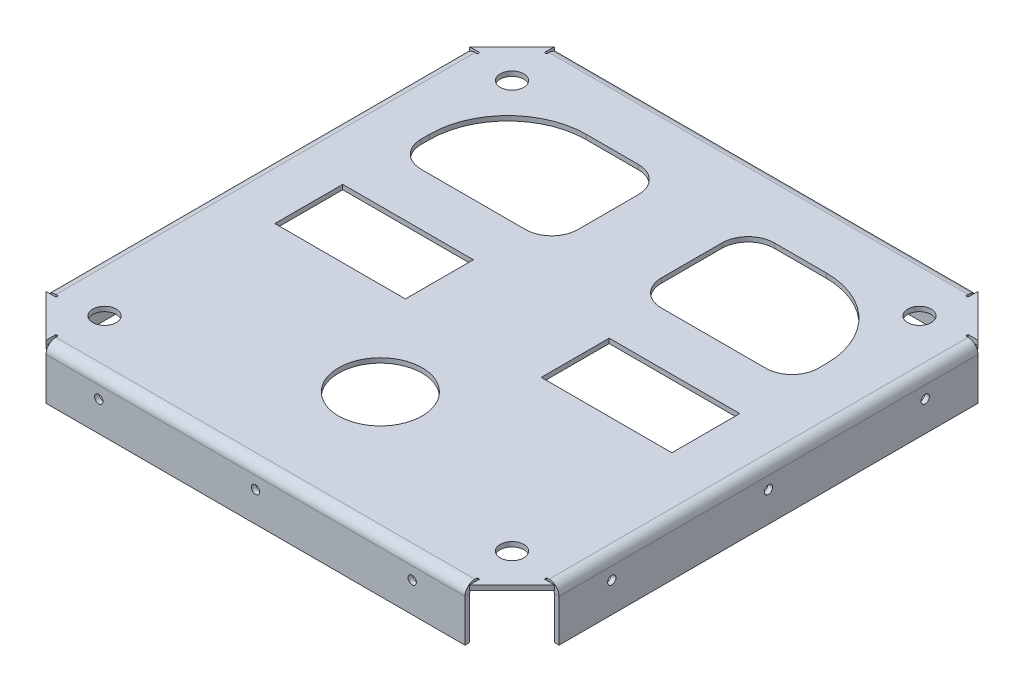
SolidWorks part; units mm, degrees
note: The reader was unsure of these and kept them because the rebuilt part matched: flange length of "Edge-Flange1".
material "6061 Alloy"
ref_plane "Front Plane" through (0, 0, 0) normal (0, 0, 1) x (1, 0, 0)
ref_plane "Top Plane" through (0, 0, 0) normal (0, 1, 0) x (1, 0, 0)
ref_plane "Right Plane" through (0, 0, 0) normal (1, 0, 0) x (0, 0, -1)
sketch "Sketch1" plane through (0, 0, 0) normal (0, 1, 0) x (1, 0, 0)
  line L0 (9, 98.2) -> (0, 89.2)
  line L1 (9, 98.2) -> (89.2, 98.2)
  line L2 (0, 89.2) -> (0, 9)
  line L3 (9, 0) -> (89.2, 0)
  line L4 (98.2, 89.2) -> (98.2, 9)
  line L5 (89.2, 98.2) -> (98.2, 89.2)
  line L6 (98.2, 9) -> (89.2, 0)
  line L7 (9, 0) -> (0, 9)
  line L8 (49.1, 98.2) -> (49.1, 0) construction
  line L9 (87.1, 54.7) -> (87.1, 41.7)
  line L10 (36.1, 54.7) -> (11.1, 54.7)
  line L11 (36.1, 54.7) -> (36.1, 41.7)
  line L12 (36.1, 41.7) -> (11.1, 41.7)
  line L13 (11.1, 54.7) -> (11.1, 41.7)
  line L14 (62.1, 41.7) -> (87.1, 41.7)
  line L15 (62.1, 54.7) -> (62.1, 41.7)
  line L16 (62.1, 54.7) -> (87.1, 54.7)
  dimension "D1" = 98.2
  dimension "D2" = 98.2
  dimension "D3" = 9
  dimension "D4" = 9
  dimension "D5" = 9
  dimension "D6" = 9
  dimension "D7" = 43.5
  dimension "D8" = 56.5
  dimension "D9" = 13
  dimension "D10" = 38
base flange "Base-Flange1" sketch "Sketch1" thickness 0.9 reverse thickness direction no parameters "D1"=1
edge flange "Edge-Flange1" sketch "Sketch14" flange profiles "Sketch14", "Sketch15", "Sketch16", "Sketch17" flange angle 90 flange length 10 flange position material inside bend radius 1 thickness 0.9 relief rectangular parameters "D6"=10, "D8"=1
sketch "Sketch14" plane through (98.2, -0.9, 0) normal (-1, 0, 0) x (0, 0, -1)
  line L1 (89.2, 0) -> (9, 0) construction
  line L2 (9, 0) -> (9, 9.1)
  line L3 (9, 9.1) -> (89.2, 9.1)
  line L4 (89.2, 9.1) -> (89.2, 0)
  line L5 (89.2, 0) -> (9, 0)
sketch "Sketch15" plane through (0, -0.9, 0) normal (0, 0, -1) x (1, 0, 0)
  line L0 (89.2, 0) -> (9, 0) construction
  line L1 (89.2, 0) -> (9, 0)
  line L2 (89.2, 0) -> (89.2, 9.1)
  line L3 (89.2, 9.1) -> (9, 9.1)
  line L4 (9, 9.1) -> (9, 0)
sketch "Sketch16" plane through (0, -0.9, 0) normal (1, 0, 0) x (0, 0, 1)
  line L0 (-9, 0) -> (-89.2, 0) construction
  line L1 (-9, 0) -> (-89.2, 0)
  line L2 (-9, 0) -> (-9, 9.1)
  line L3 (-9, 9.1) -> (-89.2, 9.1)
  line L4 (-89.2, 9.1) -> (-89.2, 0)
sketch "Sketch17" plane through (0, -0.9, -98.2) normal (0, 0, 1) x (-1, 0, 0)
  line L0 (-9, 0) -> (-89.2, 0) construction
  line L1 (-9, 0) -> (-89.2, 0)
  line L2 (-9, 0) -> (-9, 9.1)
  line L3 (-9, 9.1) -> (-89.2, 9.1)
  line L4 (-89.2, 9.1) -> (-89.2, 0)
bend "EdgeBend1" bend radius 1 bend angle 90 parameters "D5"=1
bend "EdgeBend2" bend radius 1 bend angle 90 parameters "D5"=2
bend "EdgeBend3" bend radius 1 bend angle 90 parameters "D5"=3
bend "EdgeBend4" bend radius 1 bend angle 90 parameters "D5"=4
sketch "Sketch18" plane through (0, 0, 0) normal (0, 1, 0) x (1, 0, 0)
  line L1 (9, 1.9) -> (89.2, 1.9) construction
  line L5 (11.1, 69.7) -> (11.1, 71.3)
  line L6 (89.2, 96.3) -> (9, 96.3) construction
  line L7 (26.1, 86.3) -> (36.1, 86.3)
  line L8 (41.1, 81.3) -> (41.1, 69.7)
  line L9 (36.1, 64.7) -> (16.1, 64.7)
  line L10 (49.1, 96.3) -> (49.1, 1.9) construction
  line L12 (62.1, 64.7) -> (82.1, 64.7)
  line L13 (57.1, 81.3) -> (57.1, 69.7)
  line L14 (72.1, 86.3) -> (62.1, 86.3)
  line L15 (87.1, 69.7) -> (87.1, 71.3)
  line L18 (36.1, 54.7) -> (11.1, 54.7) construction
  circle A0 centre (49.1, 23.9) radius 8
  arc A4 (36.1, 64.7) -> (41.1, 69.7) centre (36.1, 69.7) ccw
  arc A5 (16.1, 64.7) -> (11.1, 69.7) centre (16.1, 69.7) cw
  arc A7 (36.1, 86.3) -> (41.1, 81.3) centre (36.1, 81.3) cw
  arc A8 (62.1, 86.3) -> (57.1, 81.3) centre (62.1, 81.3) ccw
  arc A10 (82.1, 64.7) -> (87.1, 69.7) centre (82.1, 69.7) ccw
  arc A11 (62.1, 64.7) -> (57.1, 69.7) centre (62.1, 69.7) cw
  arc A16 (11.1, 71.3) -> (26.1, 86.3) centre (26.1, 71.3) cw
  arc A17 (87.1, 71.3) -> (72.1, 86.3) centre (72.1, 71.3) ccw
  dimension "D8" = 15
  dimension "D9" = 15
  dimension "D4" = 16
  dimension "D1" = 10
  dimension "D2" = 10
  dimension "D3" = 8
  dimension "D5" = 22
extrude "Cut-Extrude1" cut sketch "Sketch18" against normal blind 10 normal cut yes
hole_wizard "M2x0.4 Tapped Hole1" positions "Sketch21" profile "Sketch22" tap size "M2x0.4" standard "ANSI Metric"
sketch "Sketch21" plane through (102.3843, -9.7238, 0) normal (0, 0, 1) x (1, 0, 0)
  point P0 (-83.2843, 5.4738)
  point P1 (-53.2843, 5.4738)
  point P2 (-23.2843, 5.4738)
cosmetic thread "Hole Thread1"
cosmetic thread "Hole Thread2"
cosmetic thread "Hole Thread3"
sketch "Sketch22" plane through (19.1, -4.25, 0) normal (1, 0, 0) x (0, -1, 0)
  line L0 (0, 0) -> (0, 5.6807)
  line L1 (0, 5.6807) -> (0.8, 5.2)
  line L2 (0.8, 5.2) -> (0.8, 0)
  line L5 (0.8, 0) -> (0, 0)
  line L10 (0, 5.6807) -> (-0.8, 5.2) construction
  line L11 (0, -6.35) -> (0, 107.95) construction
  dimension "Tap Drill Dia." = 1.6
  dimension "Tap Drill Depth" = 5.2
  dimension "Drill Angle" = 118
hole_wizard "M2x0.4 Tapped Hole2" positions "Sketch23" profile "Sketch24" tap size "M2x0.4" standard "ANSI Metric"
sketch "Sketch23" plane through (0, -9.7238, -74.0081) normal (-1, 0, 0) x (0, 0, 1)
  point P0 (54.9081, 5.4738)
  point P1 (24.9081, 5.4738)
  point P2 (-5.0919, 5.4738)
sketch "Sketch24" plane through (0, -4.25, -19.1) normal (0, 1, 0) x (0, 0, 1)
  line L0 (0, 0) -> (0, 5.6807)
  line L1 (0, 5.6807) -> (0.8, 5.2)
  line L2 (0.8, 5.2) -> (0.8, 0)
  line L5 (0.8, 0) -> (0, 0)
  line L10 (0, 5.6807) -> (-0.8, 5.2) construction
  line L11 (0, -6.35) -> (0, 107.95) construction
  dimension "Tap Drill Dia." = 1.6
  dimension "Tap Drill Depth" = 5.2
  dimension "Drill Angle" = 118
cosmetic thread "Hole Thread4"
cosmetic thread "Hole Thread5"
cosmetic thread "Hole Thread6"
hole_wizard "M2x0.4 Tapped Hole3" positions "Sketch25" profile "Sketch26" tap size "M2x0.4" standard "ANSI Metric"
sketch "Sketch25" plane through (102.3843, -9.7238, -98.2) normal (0, 0, -1) x (-1, 0, 0)
  point P0 (23.2843, 5.4738)
  point P1 (53.2843, 5.4738)
  point P2 (83.2843, 5.4738)
sketch "Sketch26" plane through (79.1, -4.25, -98.2) normal (1, 0, 0) x (0, 1, 0)
  line L0 (0, 0) -> (0, 5.6807)
  line L1 (0, 5.6807) -> (0.8, 5.2)
  line L2 (0.8, 5.2) -> (0.8, 0)
  line L5 (0.8, 0) -> (0, 0)
  line L10 (0, 5.6807) -> (-0.8, 5.2) construction
  line L11 (0, -6.35) -> (0, 107.95) construction
  dimension "Tap Drill Dia." = 1.6
  dimension "Tap Drill Depth" = 5.2
  dimension "Drill Angle" = 118
cosmetic thread "Hole Thread7"
cosmetic thread "Hole Thread8"
cosmetic thread "Hole Thread9"
hole_wizard "M2x0.4 Tapped Hole4" positions "Sketch27" profile "Sketch28" tap size "M2x0.4" standard "ANSI Metric"
sketch "Sketch27" plane through (98.2, -9.7238, -74.0081) normal (1, 0, 0) x (0, 0, -1)
  point P0 (-24.9081, 5.4738)
  point P1 (5.0919, 5.4738)
  point P2 (-54.9081, 5.4738)
sketch "Sketch28" plane through (98.2, -4.25, -49.1) normal (0, 1, 0) x (0, 0, -1)
  line L0 (0, 0) -> (0, 5.6807)
  line L1 (0, 5.6807) -> (0.8, 5.2)
  line L2 (0.8, 5.2) -> (0.8, 0)
  line L5 (0.8, 0) -> (0, 0)
  line L10 (0, 5.6807) -> (-0.8, 5.2) construction
  line L11 (0, -6.35) -> (0, 107.95) construction
  dimension "Tap Drill Dia." = 1.6
  dimension "Tap Drill Depth" = 5.2
  dimension "Drill Angle" = 118
cosmetic thread "Hole Thread10"
cosmetic thread "Hole Thread11"
cosmetic thread "Hole Thread12"
hole_wizard "M4 Clearance Hole1" positions "Sketch29" profile "Sketch30" hole size "M4" standard "ANSI Metric" end condition through all
sketch "Sketch29" plane through (102.3843, 0, -74.0081) normal (0, 1, 0) x (1, 0, 0)
  point P0 (-92.2843, 14.0919)
  point P1 (-92.2843, -63.9081)
  point P2 (-14.2843, -63.9081)
  point P3 (-14.2843, 14.0919)
sketch "Sketch30" plane through (10.1, 0, -88.1) normal (1, 0, 0) x (0, 0, 1)
  line L0 (0, 0) -> (0, 10)
  line L1 (0, 10) -> (2.25, 10)
  line L2 (2.25, 10) -> (2.25, 0)
  line L3 (2.25, 0) -> (0, 0)
  line L4 (0, -6.35) -> (0, 107.95) construction
  dimension "Thru Hole Dia." = 4.5
  dimension "Thru Hole Depth" = 10
sketch "Bend-Lines1" plane through (0, 0, 0) normal (0, 1, 0) x (1, 0, 0)
sketch "Bounding-Box1" plane through (0, 0, 0) normal (0, 1, 0) x (1, 0, 0)
sheet metal parameters "Sheet-Metal1" thickness 0.9 parameters "D1"=1
flat pattern "Flat-Pattern1" [suppressed]
sketch "Bend-Lines2" plane through (0, 0, 0) normal (0, 1, 0) x (1, 0, 0)
sketch "Bounding-Box2" [suppressed] plane through (0, 0, 0) normal (0, 1, 0) x (1, 0, 0)
sheet metal parameters "Sheet-Metal2" thickness 0.9 parameters "D1"=1
flat pattern "Flat-Pattern1" [suppressed]
sketch "Bend-Lines2" plane through (0, 0, 0) normal (0, 1, 0) x (1, 0, 0)
sketch "Bounding-Box2" [suppressed] plane through (0, 0, 0) normal (0, 1, 0) x (1, 0, 0)
bend of the flat pattern "Flatten-<EdgeBend1>1"
bend of the flat pattern "Flatten-<EdgeBend2>1"
bend of the flat pattern "Flatten-<EdgeBend3>1"
bend of the flat pattern "Flatten-<EdgeBend4>1"
sheet metal parameters "Sheet-Metal3" thickness 0.9 parameters "D1"=1
flat pattern "Flat-Pattern1" [suppressed]
sketch "Bend-Lines2" plane through (0, 0, 0) normal (0, 1, 0) x (1, 0, 0)
sketch "Bounding-Box2" [suppressed] plane through (0, 0, 0) normal (0, 1, 0) x (1, 0, 0)
bend of the flat pattern "Flatten-<EdgeBend1>1"
bend of the flat pattern "Flatten-<EdgeBend2>1"
bend of the flat pattern "Flatten-<EdgeBend3>1"
bend of the flat pattern "Flatten-<EdgeBend4>1"
sheet metal parameters "Sheet-Metal5" thickness 0.9 parameters "D1"=1
flat pattern "Flat-Pattern1" [suppressed]
sketch "Bend-Lines2" plane through (0, 0, 0) normal (0, 1, 0) x (1, 0, 0)
sketch "Bounding-Box2" [suppressed] plane through (0, 0, 0) normal (0, 1, 0) x (1, 0, 0)
bend of the flat pattern "Flatten-<EdgeBend1>1"
bend of the flat pattern "Flatten-<EdgeBend2>1"
bend of the flat pattern "Flatten-<EdgeBend3>1"
bend of the flat pattern "Flatten-<EdgeBend4>1"
sheet metal parameters "Sheet-Metal6" thickness 0.9 parameters "D1"=1
flat pattern "Flat-Pattern1" [suppressed]
sketch "Bend-Lines2" plane through (0, 0, 0) normal (0, 1, 0) x (1, 0, 0)
sketch "Bounding-Box2" [suppressed] plane through (0, 0, 0) normal (0, 1, 0) x (1, 0, 0)
bend of the flat pattern "Flatten-<EdgeBend1>1"
bend of the flat pattern "Flatten-<EdgeBend2>1"
bend of the flat pattern "Flatten-<EdgeBend3>1"
bend of the flat pattern "Flatten-<EdgeBend4>1"
sheet metal parameters "Sheet-Metal7" thickness 0.9 parameters "D1"=1
flat pattern "Flat-Pattern1" [suppressed]
sketch "Bend-Lines2" plane through (0, 0, 0) normal (0, 1, 0) x (1, 0, 0)
sketch "Bounding-Box2" [suppressed] plane through (0, 0, 0) normal (0, 1, 0) x (1, 0, 0)
bend of the flat pattern "Flatten-<EdgeBend1>1"
bend of the flat pattern "Flatten-<EdgeBend2>1"
bend of the flat pattern "Flatten-<EdgeBend3>1"
bend of the flat pattern "Flatten-<EdgeBend4>1"
sheet metal parameters "Sheet-Metal8" thickness 0.9 parameters "D1"=1
flat pattern "Flat-Pattern1" [suppressed]
sketch "Bend-Lines2" plane through (0, 0, 0) normal (0, 1, 0) x (1, 0, 0)
sketch "Bounding-Box2" [suppressed] plane through (0, 0, 0) normal (0, 1, 0) x (1, 0, 0)
bend of the flat pattern "Flatten-<EdgeBend1>1"
bend of the flat pattern "Flatten-<EdgeBend2>1"
bend of the flat pattern "Flatten-<EdgeBend3>1"
bend of the flat pattern "Flatten-<EdgeBend4>1"
sheet metal parameters "Sheet-Metal9" thickness 0.9 parameters "D1"=1
flat pattern "Flat-Pattern1"
sketch "Bend-Lines2" plane through (0, 0, 0) normal (0, 1, 0) x (1, 0, 0)
  line L0 (89.2, 97.4388) -> (9, 97.4388) construction
  line L1 (0.7612, 89.2) -> (0.7612, 9) construction
  line L2 (9, 0.7612) -> (89.2, 0.7612) construction
  line L3 (97.4388, 9) -> (97.4388, 89.2) construction
  line L4 (89.2, 97.4388) -> (9, 97.4388) construction
  line L5 (0.7612, 89.2) -> (0.7612, 9) construction
  line L6 (9, 0.7612) -> (89.2, 0.7612) construction
  line L7 (97.4388, 9) -> (97.4388, 89.2) construction
sketch3d "Bounding-Box2" [suppressed]
  line L0 (-8.4777, -8.4777, 0) -> (-8.4777, 106.6777, 0) construction
  line L1 (106.6777, -8.4777, 0) -> (106.6777, 106.6777, 0) construction
  line L2 (-8.4777, -8.4777, 0) -> (106.6777, -8.4777, 0) construction
  line L3 (-8.4777, 106.6777, 0) -> (106.6777, 106.6777, 0) construction
bend of the flat pattern "Flatten-<EdgeBend1>1"
bend of the flat pattern "Flatten-<EdgeBend2>1"
bend of the flat pattern "Flatten-<EdgeBend3>1"
bend of the flat pattern "Flatten-<EdgeBend4>1"
